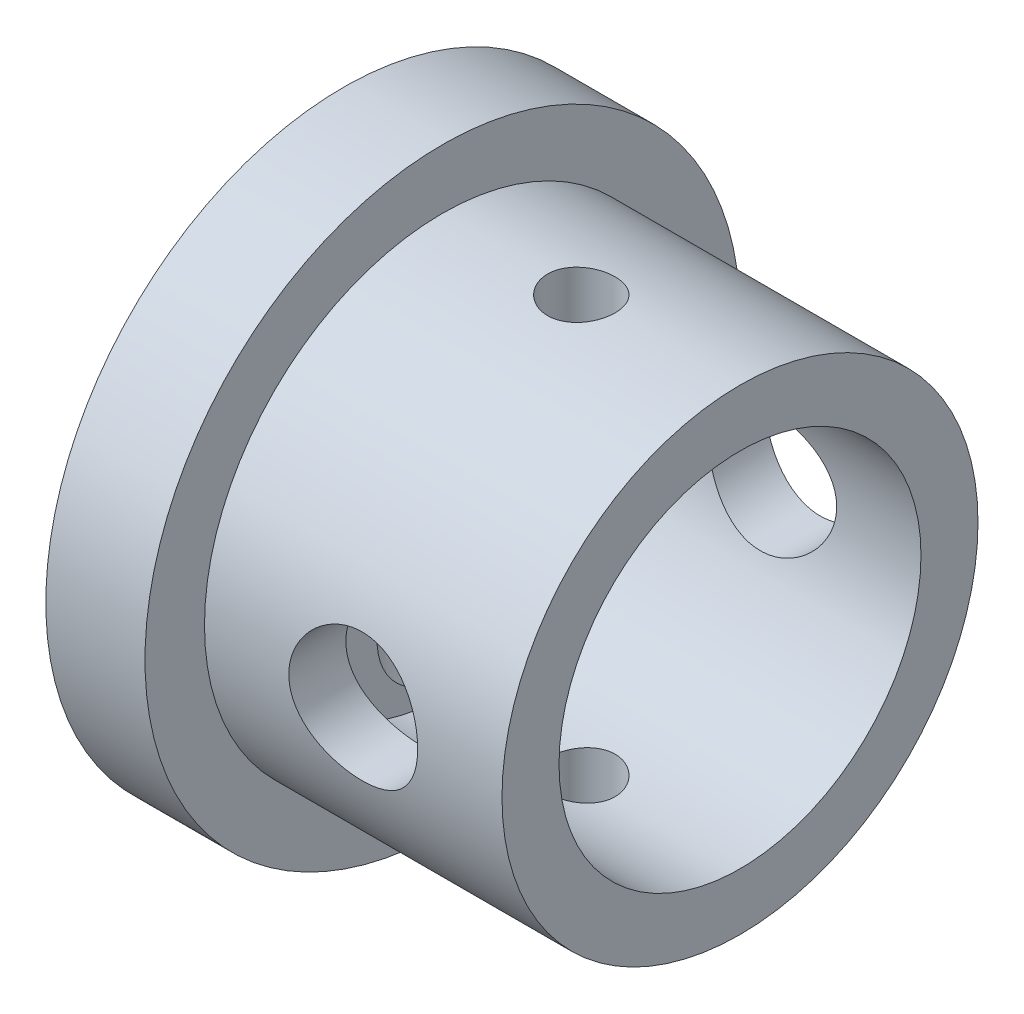
SolidWorks part; units mm, degrees
ref_plane "前视基准面" through (0, 0, 0) normal (0, 0, 1) x (1, 0, 0)
ref_plane "上视基准面" through (0, 0, 0) normal (0, 1, 0) x (1, 0, 0)
ref_plane "右视基准面" through (0, 0, 0) normal (1, 0, 0) x (0, 0, -1)
other "Configuration Table"
sketch "草图1" plane through (0, 0, 0) normal (1, 0, 0) x (0, 0, -1)
  circle A0 centre (0, 0) radius 15
  circle A1 centre (0, 0) radius 12
  circle A2 centre (0, 0) radius 9.125
  dimension "D1" = 30
  dimension "D2" = 24
  dimension "D3" = 18.25
extrude "凸台-拉伸1" add sketch "草图1" along normal blind 5 contours A0 A1 | A1 A2 | A2 region at (0, 0, 14.5757) region at (0, 0, 11.6606) region at (0, 0, 0)
extrude "凸台-拉伸2" add sketch "草图1<5>" along normal blind 20 contours A1 A2 region at (0, 0, 11.6606)
sketch "草图1<5>" plane through (0, 0, 0) normal (1, 0, 0) x (0, 0, -1) same geometry as "草图1"
hole_wizard "M3 十字槽沉头木螺钉的锥形沉头孔1" positions "草图2" profile "草图3" countersink size "M3" standard "GB" end condition through all
sketch "草图2" plane through (5, 0, 0) normal (-1, 0, 0) x (0, 0, 1)
  circle A0 centre (0, 0) radius 9.125 construction
  circle A1 centre (0, 0) radius 5
  point P0 (0, 5)
  point P3 (-5, 0)
  point P6 (0, -5)
  point P24 (5, 0)
  dimension "D1" = 10
sketch "草图3" plane through (5, 5, 0) normal (0, 1, 0) x (0, 0, -1)
  line L0 (0, 0) -> (0, 5)
  line L1 (0, 5) -> (1.7, 5)
  line L2 (1.7, 5) -> (1.7, 1.6)
  line L3 (1.7, 1.6) -> (3.3, 0)
  line L5 (3.3, 0) -> (0, 0)
  line L6 (-1.7, 1.6) -> (-3.3, 0) construction
  line L11 (0, -6.35) -> (0, 107.95) construction
  dimension "通孔孔直径" = 3.4
  dimension "通孔孔深度" = 5
  dimension "近端锥形沉头孔直径" = 6.6
  dimension "近端锥形沉头孔角度" = 90
ref_plane "基准面1" through (0, -12, 0) normal (0, -1, 0) x (-1, 0, 0)
sketch "Sketch1" plane through (0, 0, 0) normal (0, 0, 1) x (1, 0, 0)
  line L0 (20, 0) -> (12.5, 0) construction
  line L1 (20, -12) -> (20, 12) construction
  line L2 (12.5, 0) -> (5, 0) construction
  line L3 (5, -12) -> (5, 12) construction
  circle A0 centre (12.5, 0) radius 3.25
  dimension "D1" = 6.5
extrude "Cut-Extrude1" cut sketch "Sketch1" against normal through all both and the other way through all
hole_wizard "M3 Clearance Hole1" positions "Sketch2" profile "Sketch3" hole size "M3" standard "GB"
sketch "Sketch2" plane through (0, -12, 0) normal (0, -1, 0) x (-1, 0, 0)
  line L0 (0, -15) -> (0, 15) construction
  point P0 (-12, 0)
  dimension "D1" = 12
sketch "Sketch3" plane through (12, -12, 0) normal (1, 0, 0) x (0, 0, -1)
  line L0 (0, 0) -> (0, 36.0215)
  line L1 (0, 36.0215) -> (1.7, 35)
  line L2 (1.7, 35) -> (1.7, 0)
  line L5 (1.7, 0) -> (0, 0)
  line L10 (0, 36.0215) -> (-1.7, 35) construction
  line L11 (0, -6.35) -> (0, 107.95) construction
  dimension "Hole Dia." = 3.4
  dimension "Hole Depth" = 35
  dimension "Drill Angle" = 118
